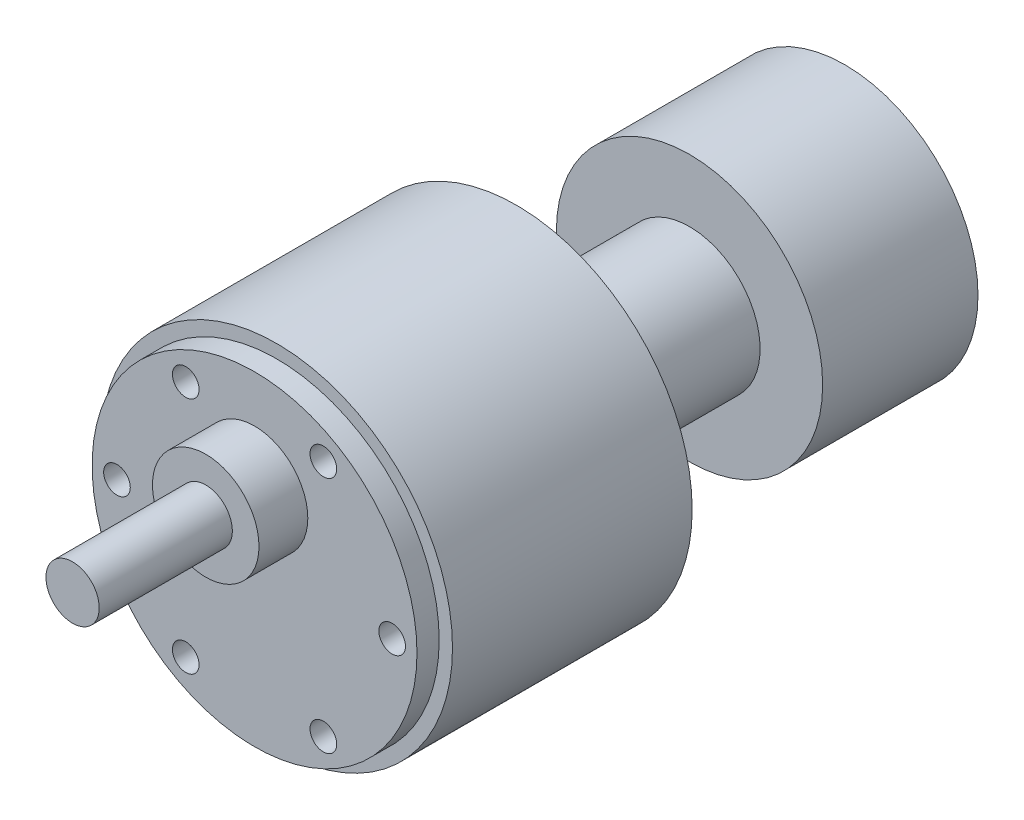
SolidWorks part; units mm, degrees
ref_plane "Front Plane" through (0, 0, 0) normal (0, 0, 1) x (1, 0, 0)
ref_plane "Top Plane" through (0, 0, 0) normal (0, 1, 0) x (1, 0, 0)
ref_plane "Right Plane" through (0, 0, 0) normal (1, 0, 0) x (0, 0, -1)
sketch "Sketch4" plane through (0, 0, 0) normal (0, 0, 1) x (1, 0, 0)
  circle A0 centre (0, 0) radius 7.9537
  dimension "D1" = 15.9075
extrude "Boss-Extrude4" add sketch "Sketch4" along normal mid plane 66.5
ref_plane "Plane3" through (0, 0, 30.75) normal (0, 0, 1) x (1, 0, 0)
sketch "Sketch5" plane through (0, 0, 30.75) normal (0, 0, 1) x (1, 0, 0)
  circle A0 centre (0, 0) radius 19.8
  circle A1 centre (0, 0) radius 18.3
  dimension "D2" = 36.6
  dimension "MotorMaxDiameter" = 39.6
extrude "Boss-Extrude5" add sketch "Sketch5" along normal blind 2.5 contours A1 region at (0, 0, 30.75)
extrude "Boss-Extrude6" add sketch "Sketch5<3>" against normal blind 27 contours A1 | A0 A1 region at (-19.24, 0, 30.75) region at (0, 0, 30.75)
sketch "Sketch5<3>" plane through (0, 0, 30.75) normal (0, 0, 1) x (1, 0, 0) same geometry as "Sketch5"
sketch "Sketch6" plane through (0, 0, -33.25) normal (0, 0, -1) x (-1, 0, 0)
  circle A0 centre (0, 0) radius 15
  dimension "D1" = 30
extrude "Boss-Extrude7" add sketch "Sketch6" against normal blind 17.5
ref_axis "Axis1" through (0, 0, 64.6975) along (0, 0, -1)
sketch "Sketch7" plane through (0, 0, 33.25) normal (0, 0, 1) x (1, 0, 0)
  circle A0 centre (0, 7) radius 6
  dimension "MotorShaftOffset" = 7
  dimension "MotorFrontBossDiameter" = 12
extrude "Boss-Extrude8" add sketch "Sketch7" along normal blind 5.5
ref_point "Point1"
sketch "Sketch9" plane through (0, 0, 38.75) normal (0, 0, 1) x (1, 0, 0)
  circle A0 centre (0, 7) radius 3
  dimension "D1" = 6
extrude "Boss-Extrude9" add sketch "Sketch9" along normal blind 15
sketch "Sketch10" plane through (0, 0, 33.25) normal (0, 0, 1) x (1, 0, 0)
  line L0 (-15.5, 0) -> (15.5, 0) construction
  circle A0 centre (0, 0) radius 15.5 construction
  circle A1 centre (-15.5, 0) radius 1.5
  dimension "D1" = 31
  dimension "D2" = 3
extrude "Cut-Extrude1" cut sketch "Sketch10" against normal blind 4 contours A1
pattern_circular "CirPattern1" count 6 over 360 about axis through (0, 0, 64.6975) along (0, 0, -1) of "Cut-Extrude1"
sketch "Sketch11" plane through (0, 0, 33.25) normal (0, 0, 1) x (1, 0, 0)
  line L0 (0, 18.3) -> (0, -18.3) construction
  line L1 (-18.3, 0) -> (18.3, 0) construction
  circle A0 centre (0, 0) radius 18.3 construction
  circle A1 centre (0, 0) radius 18.3 construction
sketch "Sketch12" plane through (0, 0, 38.75) normal (0, 0, 1) x (1, 0, 0)
  line L0 (0, 13) -> (0, 1) construction
  line L1 (0, 18.3) -> (0, -18.3) construction
  line L2 (6, 7) -> (-6, 7) construction
  circle A0 centre (0, 7) radius 6 construction
  circle A1 centre (0, 7) radius 6 construction
sketch "Sketch13" plane through (0, 0, 53.75) normal (0, 0, 1) x (1, 0, 0)
  line L0 (0, 10) -> (0, 4) construction
  line L1 (0, 18.3) -> (0, -18.3) construction
  line L2 (-3, 7) -> (3, 7) construction
  line L3 (6, 7) -> (-6, 7) construction
  circle A0 centre (0, 7) radius 3 construction
  circle A1 centre (0, 7) radius 3 construction
